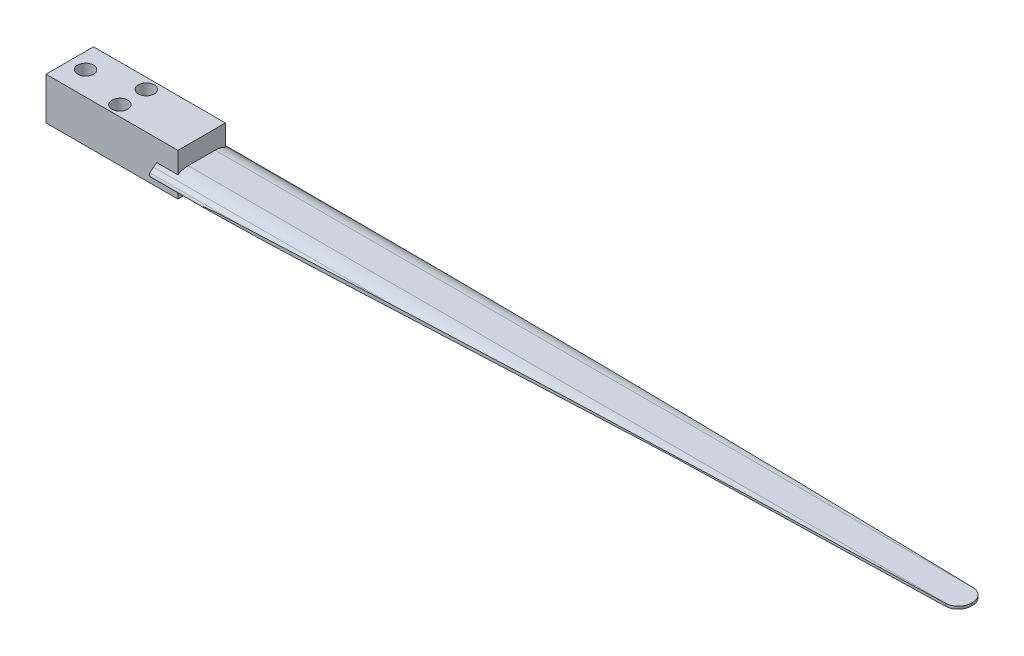
SolidWorks part; units mm, degrees
material "1350 Alloy"
ref_plane "Front Plane" through (0, 0, 0) normal (0, 0, 1) x (1, 0, 0)
ref_plane "Top Plane" through (0, 0, 0) normal (0, 1, 0) x (1, 0, 0)
ref_plane "Right Plane" through (0, 0, 0) normal (1, 0, 0) x (0, 0, -1)
sketch "Sketch1" plane through (0, 0, 0) normal (1, 0, 0) x (0, 0, -1)
  line L0 (0, 0) -> (40, 0)
  line L1 (40, 0) -> (61.9478, -18.4164)
  line L6 (0, -5) -> (38.1801, -5)
  line L7 (38.1801, -5) -> (58.7339, -22.2466)
  line L8 (61.9478, -18.4164) -> (58.7339, -22.2466)
  line L9 (0, 0) -> (0, -5) construction
  line L10 (-61.9478, -18.4164) -> (-58.7339, -22.2466)
  line L11 (-38.1801, -5) -> (-58.7339, -22.2466)
  line L12 (0, -5) -> (-38.1801, -5)
  line L13 (-40, 0) -> (-61.9478, -18.4164)
  line L14 (0, 0) -> (-40, 0)
  dimension "D1" = 40
  dimension "D2" = 40
  dimension "D3" = 5
extrude "Boss-Extrude1" add sketch "Sketch1" along normal blind 1500
fillet "Fillet1" radius 40 2 edges at (750, -5, -38.1801) (750, 0, 40)
fillet "Fillet2" radius 40 1 edges at (750, 0, -40)
fillet "Fillet3" radius 5 4 edges at (750, -22.2466, -58.7339) (1500, -20.3315, -60.3408) (750, -18.4164, -61.9478) (0, -20.3315, -60.3408)
fillet "Fillet4" radius 5 4 edges at (750, -18.4164, 61.9478) (1500, -20.3315, 60.3408) (750, -22.2466, 58.7339) (0, -20.3315, 60.3408)
sketch "Sketch2" plane through (0, 0, 0) normal (0, 1, 0) x (1, 0, 0)
  line L0 (1500, 25.4412) -> (101.5743, 59.9036)
  line L1 (1498.2139, 59.9036) -> (1.7861, 59.9036) construction
  line L2 (101.5743, 59.9036) -> (1500, 59.9036)
  line L3 (1500, 59.9036) -> (1500, 25.4412)
  line L4 (0, 0) -> (60.5883, 0)
  line L5 (1500, -59.9036) -> (1500, -25.4412)
  line L6 (101.5743, -59.9036) -> (1500, -59.9036)
  line L7 (1500, -25.4412) -> (101.5743, -59.9036)
extrude "Cut-Extrude1" cut sketch "Sketch2" against normal through all both contours L5 L7 L6 | L3 L2 L0 region at (1033.8581, 0, -48.4162) region at (1033.8581, 0, 48.4162)
fillet "Fillet5" radius 25 2 edges at (1500, -2.5207, -25.4412) (1500, -2.5, 25.4412)
sketch "Sketch3" plane through (0, 0, 0) normal (0, 1, 0) x (1, 0, 0)
  line L1 (40, 45) -> (-210, 45)
  line L2 (40, 45) -> (40, -45)
  line L3 (40, -45) -> (-210, -45)
  line L4 (-210, 45) -> (-210, -45)
  circle A0 centre (-180, 0) radius 15
  circle A1 centre (-90, 25) radius 15
  circle A2 centre (-90, -25) radius 15
  dimension "D3" = 30
  dimension "D1" = 250
  dimension "D2" = 210
  dimension "D4" = 90
  dimension "D5" = 45
  dimension "D6" = 25
  dimension "D7" = 25
  dimension "D8" = 90
  dimension "D9" = 180
extrude "Boss-Extrude2" add sketch "Sketch3" against normal blind 45 and the other way blind 35
